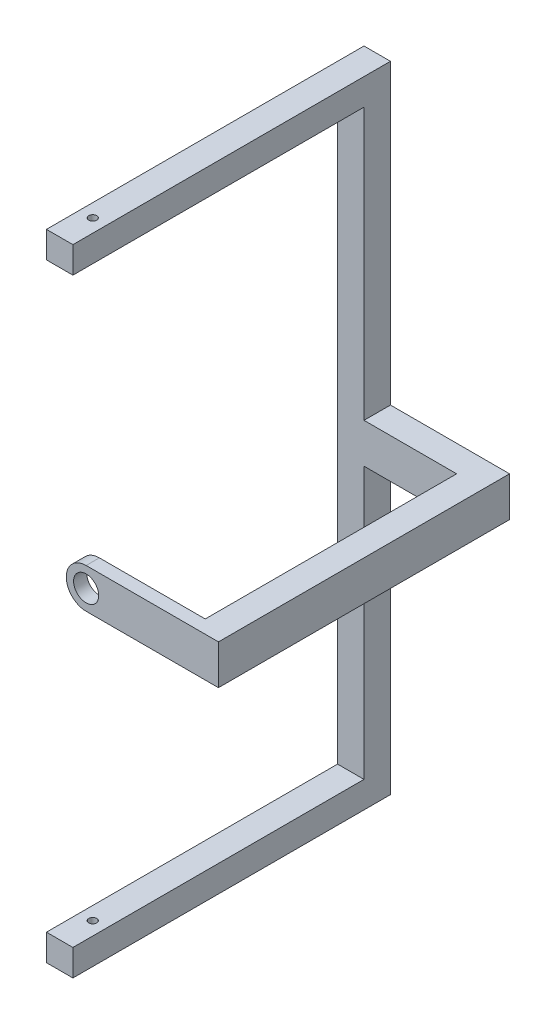
SolidWorks part; units mm, degrees
ref_plane "前视基准面" through (0, 0, 0) normal (0, 0, 1) x (1, 0, 0)
ref_plane "上视基准面" through (0, 0, 0) normal (0, 1, 0) x (1, 0, 0)
ref_plane "右视基准面" through (0, 0, 0) normal (1, 0, 0) x (0, 0, -1)
other "Configuration Table"
sketch "草图1" plane through (0, 0, 0) normal (0, 0, 1) x (1, 0, 0)
  line L0 (0, 15) -> (100, 15)
  line L1 (100, 15) -> (100, -15)
  line L2 (100, -15) -> (0, -15)
  circle A0 centre (0, 0) radius 9.5
  arc A1 (0, 15) -> (0, -15) centre (0, 0) ccw
  dimension "D1" = 19
  dimension "D2" = 30
  dimension "D3" = 100
extrude "凸台-拉伸1" add sketch "草图1" along normal blind 10
sketch "草图2" plane through (0, 0, 0) normal (0, 0, -1) x (-1, 0, 0)
  line L0 (0, -15) -> (-100, -15) construction
  line L1 (-100, 15) -> (-80, 15)
  line L2 (-100, 15) -> (-100, -15)
  line L3 (-100, -15) -> (-80, -15)
  line L4 (-80, 15) -> (-80, -15)
  dimension "D1" = 20
extrude "凸台-拉伸2" add sketch "草图2" along normal blind 210
sketch "草图3" plane through (80, 0, 0) normal (-1, 0, 0) x (0, 0, 1)
  line L0 (-210, -15) -> (0, -15) construction
  line L1 (-210, 15) -> (-190, 15)
  line L2 (-210, 15) -> (-210, -15)
  line L3 (-210, -15) -> (-190, -15)
  line L4 (-190, 15) -> (-190, -15)
  dimension "D1" = 20
extrude "凸台-拉伸3" add sketch "草图3" along normal blind 70
ref_axis "基准轴1" through (0, 0, 163.6884) along (0, 0, -1)
ref_point "点1"
ref_axis "基准轴3" through (0, -248.9161, 5) along (0, 1, 0)
ref_axis "基准轴4" through (-111.113, 0, 5) along (1, 0, 0)
sketch "草图4" plane through (10, 0, 0) normal (-1, 0, 0) x (0, 0, 1)
  line L0 (-190, 0) -> (-190, -220)
  line L1 (-190, -15) -> (-190, 15) construction
  line L2 (-190, -220) -> (30, -220)
  line L4 (30, -220) -> (30, -240)
  line L5 (30, -240) -> (-210, -240)
  line L6 (-210, -240) -> (-210, 0)
  line L7 (-210, 15) -> (-210, -15) construction
  line L8 (-210, 0) -> (-190, 0)
  dimension "D1" = 20
  dimension "D2" = 240
  dimension "D3" = 240
extrude "凸台-拉伸4" add sketch "草图4" along normal blind 20
mirror "镜向1" about plane through (-10, 0, -210) normal (0, -1, 0) of "凸台-拉伸4"
sketch "草图5" plane through (0, -220, 0) normal (0, 1, 0) x (1, 0, 0)
  circle A0 centre (0, -5) radius 3
  point P3 (0, -5)
  point P4 (0, 0)
  point P5 (0, -5)
  dimension "D1" = 6
extrude "切除-拉伸1" cut sketch "草图5" against normal blind 20
mirror "镜向2" about plane through (0, 0, 0) normal (0, 1, 0) of "切除-拉伸1"
